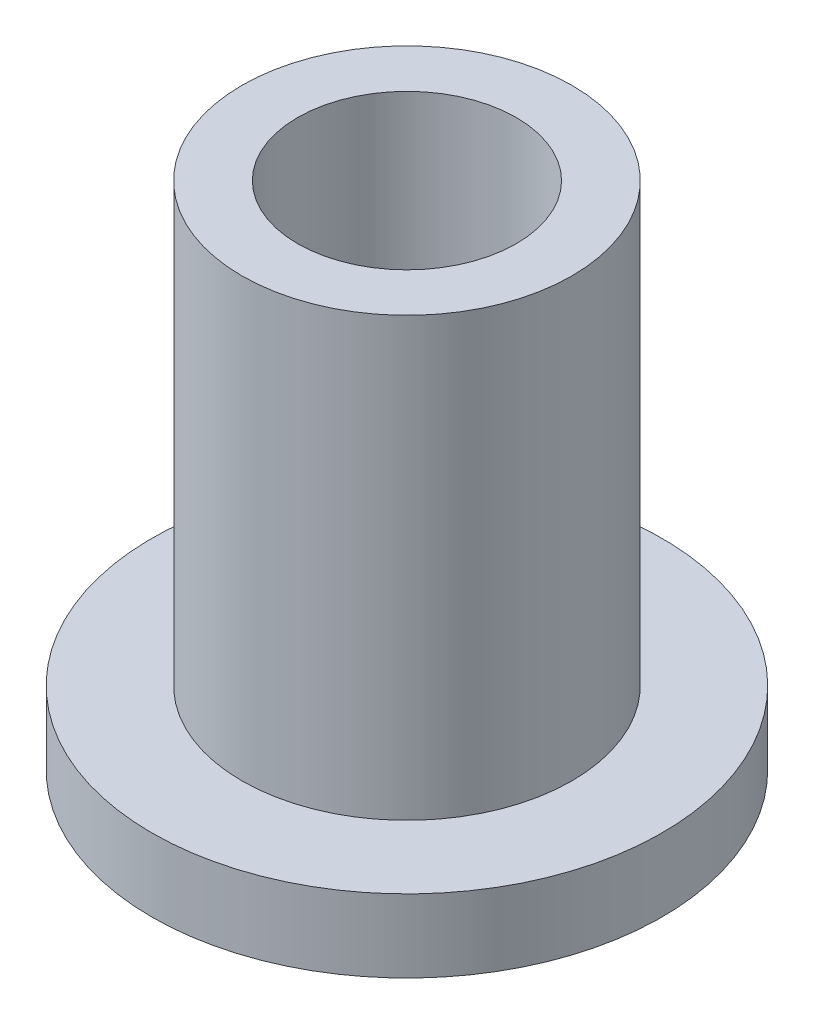
SolidWorks part; units mm, degrees
material "6061 Alloy"
ref_plane "Front Plane" through (0, 0, 0) normal (0, 0, 1) x (1, 0, 0)
ref_plane "Top Plane" through (0, 0, 0) normal (0, 1, 0) x (1, 0, 0)
ref_plane "Right Plane" through (0, 0, 0) normal (1, 0, 0) x (0, 0, -1)
sketch "Sketch1" plane through (0, 0, 0) normal (0, 1, 0) x (1, 0, 0)
  circle A0 centre (0, 0) radius 5.5562
  dimension "D1" = 11.1125
extrude "Boss-Extrude1" add sketch "Sketch1" along normal blind 1.5875
sketch "Sketch2" plane through (0, 1.5875, 0) normal (0, 1, 0) x (1, 0, 0)
  circle A1 centre (0, 0) radius 3.5941
  dimension "D2" = 7.1882
extrude "Boss-Extrude2" add sketch "Sketch2" along normal blind 9.525 contours A1 region at (0, 1.5875, 0)
sketch "Sketch3" plane through (0, 11.1125, 0) normal (0, 1, 0) x (1, 0, 0)
  circle A0 centre (0, 0) radius 2.3813
  dimension "D1" = 4.7625
extrude "Cut-Extrude1" cut sketch "Sketch3" against normal up to surface (11.1125 mm away) contours A0 region at (0, 11.1125, 0) up to face at (0, 0, 5.5562)
